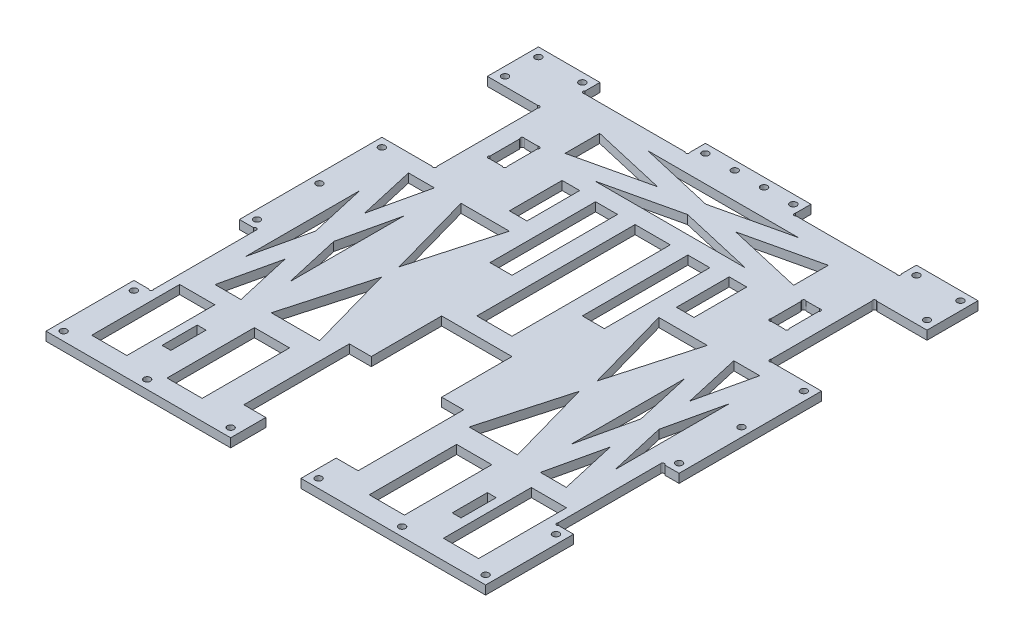
SolidWorks part; units mm, degrees
material "7050-T73510"
ref_plane "Front Plane" through (0, 0, 0) normal (0, 0, 1) x (1, 0, 0)
ref_plane "Top Plane" through (0, 0, 0) normal (0, 1, 0) x (1, 0, 0)
ref_plane "Right Plane" through (0, 0, 0) normal (1, 0, 0) x (0, 0, -1)
sketch "Sketch1" plane through (0, 0, 0) normal (0, 1, 0) x (1, 0, 0)
  line L1 (-158.75, -177.8) -> (158.75, -177.8)
  line L2 (-158.75, -177.8) -> (-158.75, 177.8)
  line L3 (-158.75, 177.8) -> (158.75, 177.8)
  line L4 (158.75, -177.8) -> (158.75, 177.8)
  line L5 (-158.75, -177.8) -> (158.75, 177.8) construction
  line L6 (-158.75, 177.8) -> (158.75, -177.8) construction
  point P0 (0, 0)
  dimension "D1" = 355.6
  dimension "D2" = 317.5
extrude "Boss-Extrude1" add sketch "Sketch1" along normal blind 6.35
sketch "Sketch2" plane through (0, 6.35, 0) normal (0, 1, 0) x (1, 0, 0)
  line L0 (-158.75, -177.8) -> (158.75, -177.8) construction
  line L1 (-25.4, -25.4) -> (25.4, -25.4)
  line L2 (-25.4, -25.4) -> (-25.4, -177.8)
  line L3 (-25.4, -177.8) -> (25.4, -177.8)
  line L4 (25.4, -25.4) -> (25.4, -177.8)
  line L5 (-25.4, -25.4) -> (25.4, -177.8) construction
  line L6 (-25.4, -177.8) -> (25.4, -25.4) construction
  point P0 (0, -101.6)
  dimension "D1" = 152.4
  dimension "D2" = 50.8
extrude "Cut-Extrude1" cut sketch "Sketch2" against normal through all
sketch "Sketch3" plane through (0, 6.35, 0) normal (0, 1, 0) x (1, 0, 0)
  line L0 (158.75, -177.8) -> (158.75, 177.8) construction
  line L5 (146.05, 140.97) -> (120.65, 140.97)
  line L11 (146.05, 140.97) -> (146.05, 64.77)
  line L13 (146.05, 64.77) -> (120.65, 64.77)
  line L15 (120.65, 140.97) -> (120.65, 64.77)
  line L16 (158.75, 177.8) -> (-158.75, 177.8) construction
  line L17 (107.95, 90.17) -> (95.25, 90.17)
  line L18 (107.95, 90.17) -> (107.95, 115.57)
  line L19 (107.95, 115.57) -> (95.25, 115.57)
  line L20 (95.25, 90.17) -> (95.25, 115.57)
  line L21 (0, -3.4925) -> (0, 3.4925) construction
  line L22 (-95.25, 90.17) -> (-95.25, 115.57)
  line L23 (-107.95, 115.57) -> (-95.25, 115.57)
  line L24 (-107.95, 90.17) -> (-107.95, 115.57)
  line L25 (-107.95, 90.17) -> (-95.25, 90.17)
  line L26 (-120.65, 140.97) -> (-120.65, 64.77)
  line L27 (-146.05, 64.77) -> (-120.65, 64.77)
  line L28 (-146.05, 140.97) -> (-146.05, 64.77)
  line L29 (-146.05, 140.97) -> (-120.65, 140.97)
  point P14 (107.95, 102.87)
  point P15 (120.65, 102.87)
  dimension "D1" = 25.4
  dimension "D2" = 12.7
  dimension "D3" = 12.7
  dimension "D4" = 12.7
  dimension "D5" = 25.4
  dimension "D6" = 76.2
  dimension "D7" = 36.83
extrude "Cut-Extrude2" cut sketch "Sketch3" against normal through all contours L5 L15 L13 L11 | L20 L17 L18 L19 | L29 L28 L27 L26 | L24 L25 L22 L23 | L26 L27 L28 L29 region at (133.35, 6.35, -102.87) region at (101.6, 6.35, -102.87) region at (-101.6, 6.35, -102.87) region at (-133.35, 6.35, -102.87)
sketch "Sketch4" plane through (0, 6.35, 0) normal (0, 1, 0) x (1, 0, 0)
  line L0 (-158.75, 177.8) -> (-158.75, -177.8) construction
  line L1 (-158.75, 140.97) -> (-146.05, 140.97)
  line L2 (-158.75, 140.97) -> (-158.75, 64.77)
  line L3 (-158.75, 64.77) -> (-146.05, 64.77)
  line L4 (-146.05, 140.97) -> (-146.05, 64.77)
  line L5 (0, -3.4925) -> (0, 3.4925) construction
  line L6 (-158.75, -114.3) -> (-146.05, -114.3)
  line L7 (-158.75, -114.3) -> (-158.75, -38.1)
  line L8 (-158.75, -38.1) -> (-146.05, -38.1)
  line L9 (-146.05, -114.3) -> (-146.05, -38.1)
  line L10 (158.75, 64.77) -> (146.05, 64.77)
  line L11 (146.05, 140.97) -> (146.05, 64.77)
  line L12 (158.75, 140.97) -> (146.05, 140.97)
  line L13 (158.75, 140.97) -> (158.75, 64.77)
  line L14 (158.75, -38.1) -> (146.05, -38.1)
  line L15 (146.05, -114.3) -> (146.05, -38.1)
  line L16 (158.75, -114.3) -> (146.05, -114.3)
  line L17 (158.75, -114.3) -> (158.75, -38.1)
  line L18 (158.75, 177.8) -> (-158.75, 177.8) construction
  line L19 (114.3, 165.1) -> (38.1, 165.1)
  line L20 (-114.3, 177.8) -> (-38.1, 177.8)
  line L21 (-114.3, 177.8) -> (-114.3, 165.1)
  line L22 (-114.3, 165.1) -> (-38.1, 165.1)
  line L23 (-38.1, 177.8) -> (-38.1, 165.1)
  line L24 (38.1, 177.8) -> (38.1, 165.1)
  line L25 (114.3, 177.8) -> (38.1, 177.8)
  line L26 (114.3, 177.8) -> (114.3, 165.1)
  line L27 (-25.4, -25.4) -> (-25.4, -177.8) construction
  line L28 (-25.4, -152.4) -> (-41.275, -152.4)
  line L29 (-25.4, -152.4) -> (-25.4, -76.2)
  line L30 (-25.4, -76.2) -> (-41.275, -76.2)
  line L31 (-41.275, -152.4) -> (-41.275, -76.2)
  line L32 (-158.75, -177.8) -> (-25.4, -177.8) construction
  line L33 (25.4, 101.6) -> (41.275, 101.6)
  line L34 (-25.4, 25.4) -> (-41.275, 25.4)
  line L35 (-25.4, 25.4) -> (-25.4, 101.6)
  line L36 (-25.4, 101.6) -> (-41.275, 101.6)
  line L37 (-41.275, 25.4) -> (-41.275, 101.6)
  line L38 (41.275, 25.4) -> (41.275, 101.6)
  line L39 (25.4, 25.4) -> (41.275, 25.4)
  line L40 (25.4, 25.4) -> (25.4, 101.6)
  line L41 (25.4, -76.2) -> (41.275, -76.2)
  line L42 (41.275, -152.4) -> (41.275, -76.2)
  line L43 (25.4, -152.4) -> (41.275, -152.4)
  line L44 (25.4, -152.4) -> (25.4, -76.2)
  dimension "D1" = 12.7
  dimension "D2" = 12.7
  dimension "D3" = 76.2
  dimension "D4" = 76.2
  dimension "D5" = 36.83
  dimension "D6" = 215.9
  dimension "D7" = 12.7
  dimension "D8" = 76.2
  dimension "D9" = 76.2
  dimension "D10" = 15.875
  dimension "D11" = 76.2
  dimension "D12" = 25.4
  dimension "D13" = 76.2
  dimension "D14" = 15.875
  dimension "D15" = 203.2
  dimension "D16" = 50.8
extrude "Cut-Extrude3" cut sketch "Sketch4" against normal through all
sketch "Sketch5" plane through (0, 6.35, 0) normal (0, 1, 0) x (1, 0, 0)
  line L0 (-41.275, -76.2) -> (-41.275, -152.4) construction
  line L5 (-41.275, 101.6) -> (-41.275, 25.4) construction
  line L6 (-85.725, -100.33) -> (-60.325, -100.33)
  line L7 (-133.35, -87.63) -> (-101.6, -87.63)
  line L8 (-133.35, -87.63) -> (-133.35, 52.07)
  line L9 (-133.35, 52.07) -> (-101.6, 52.07)
  line L10 (-101.6, -87.63) -> (-101.6, 52.07)
  line L11 (-133.35, -87.63) -> (-101.6, 52.07) construction
  line L12 (-133.35, 52.07) -> (-101.6, -87.63) construction
  line L13 (-82.55, 114.3) -> (82.55, 114.3)
  line L14 (-82.55, 114.3) -> (-82.55, 152.4)
  line L15 (-82.55, 152.4) -> (82.55, 152.4)
  line L16 (82.55, 114.3) -> (82.55, 152.4)
  line L17 (-82.55, 114.3) -> (82.55, 152.4) construction
  line L18 (-82.55, 152.4) -> (82.55, 114.3) construction
  line L23 (0, -3.4925) -> (0, 3.4925) construction
  line L24 (-12.7, -12.7) -> (12.7, -12.7)
  line L25 (-146.05, -114.3) -> (-146.05, -38.1) construction
  line L26 (-53.975, 102.87) -> (-66.675, 102.87)
  line L27 (-53.975, 102.87) -> (-53.975, 64.77)
  line L28 (-158.75, 64.77) -> (-158.75, -38.1) construction
  line L29 (-158.75, 64.77) -> (-120.65, 64.77) construction
  line L30 (-85.725, -100.33) -> (-85.725, -163.4194)
  line L31 (-12.7, -12.7) -> (-12.7, 101.6)
  line L32 (-12.7, 101.6) -> (12.7, 101.6)
  line L33 (12.7, -12.7) -> (12.7, 101.6)
  line L34 (-53.975, 64.77) -> (-66.675, 64.77)
  line L35 (-66.675, 102.87) -> (-66.675, 64.77)
  line L36 (53.975, 64.77) -> (66.675, 64.77)
  line L37 (-25.4, 25.4) -> (-25.4, 101.6) construction
  line L38 (-25.4, 101.6) -> (-41.275, 101.6) construction
  line L39 (-95.25, 90.17) -> (-95.25, 115.57) construction
  line L40 (-114.3, 165.1) -> (-38.1, 165.1) construction
  line L41 (-85.725, -163.4194) -> (-60.325, -163.4194)
  line L42 (-60.325, -100.33) -> (-60.325, -163.4194)
  line L43 (-139.5421, 50.6627) -> (-107.7921, -89.0373)
  line L44 (-127.1579, -89.0373) -> (-95.4079, 50.6627)
  line L45 (66.675, 102.87) -> (66.675, 64.77)
  line L46 (53.975, 102.87) -> (66.675, 102.87)
  line L47 (-83.9779, 146.2126) -> (81.1221, 108.1126)
  line L48 (-81.1221, 108.1126) -> (83.9779, 146.2126)
  line L49 (53.975, 102.87) -> (53.975, 64.77)
  line L50 (-88.9, -16.4414) -> (-53.975, -16.4414) construction
  line L51 (-127.1579, 53.4773) -> (-95.4079, -86.2227)
  line L52 (-139.5421, -86.2227) -> (-107.7921, 53.4773)
  line L53 (-88.9, 52.07) -> (-53.975, 52.07) construction
  line L54 (-88.9, 52.07) -> (-88.9, -84.9527) construction
  line L55 (-81.1221, 158.5874) -> (83.9779, 120.4874)
  line L56 (-83.9779, 120.4874) -> (81.1221, 158.5874)
  line L57 (-139.7, -100.33) -> (-114.3, -100.33)
  line L58 (-139.7, -100.33) -> (-139.7, -163.83)
  line L59 (-139.7, -163.83) -> (-114.3, -163.83)
  line L60 (-114.3, -100.33) -> (-114.3, -163.83)
  line L61 (-88.9, -84.9527) -> (-53.975, -84.9527)
  line L62 (-53.975, 52.07) -> (-53.975, -84.9527) construction
  line L63 (-107.95, -144.78) -> (-101.6, -144.78)
  line L64 (-107.95, -144.78) -> (-107.95, -119.38)
  line L65 (-107.95, -119.38) -> (-101.6, -119.38)
  line L66 (-101.6, -144.78) -> (-101.6, -119.38)
  line L67 (-107.95, -144.78) -> (-101.6, -119.38) construction
  line L68 (-107.95, -119.38) -> (-101.6, -144.78) construction
  line L69 (-88.9, -84.9527) -> (-71.4375, -22.7914)
  line L70 (-71.4375, -22.7914) -> (-53.975, -84.9527)
  line L71 (-88.9, 52.07) -> (-53.975, 52.07)
  line L72 (-88.9, 52.07) -> (-71.4375, -10.0914)
  line L73 (-71.4375, -10.0914) -> (-53.975, 52.07)
  point P5 (-117.475, -17.78)
  point P10 (0, 133.35)
  point P15 (0, 44.45)
  point P34 (-104.775, -132.08)
  point P45 (-33.3375, 101.6)
  point P87 (-114.3, -132.08)
  dimension "D3" = 12.7
  dimension "D4" = 19.05
  dimension "D5" = 139.7
  dimension "D6" = 25.4
  dimension "D7" = 12.7
  dimension "D8" = 31.75
  dimension "D9" = 25.4
  dimension "D10" = 12.7
  dimension "D11" = 165.1
  dimension "D12" = 12.7
  dimension "D13" = 12.7
  dimension "D14" = 12.7
  dimension "D17" = 25.4
  dimension "D18" = 63.5
  dimension "D19" = 12.7
  dimension "D20" = 6.35
  dimension "D21" = 38.1
  dimension "D22" = 38.1
  dimension "D23" = 25.4
  dimension "D15" = 114.3
  dimension "D16" = 12.7
  dimension "D24" = 12.7
  dimension "D25" = 12.7
  dimension "D26" = 12.7
  dimension "D27" = 15.3773
  dimension "D28" = 12.7
  dimension "D29" = 6.35
  dimension "D30" = 12.7
extrude "Cut-Extrude4" cut sketch "Sketch5" against normal through all contours L44 L7 L43 | L8 L52 L43 | L51 L52 L9 | L44 L51 L10 | L33 | L32 | L31 | L24 | L48 L13 L47 | L48 L55 L16 | L55 L56 L15 | L14 L56 L47 | L60 L57 L58 L59 | L63 L66 L65 L64 | L42 L6 L30 L41 | L26 L35 L34 L27 | L46 L49 L36 L45 | L61 L70 L69 | L71 L73 L72 region at (-73.025, 6.35, 131.8747) region at (-117.475, 6.35, 73.8975) region at (-130.229, 6.35, 17.78) region at (-104.721, 6.35, 17.78) region at (-117.475, 6.35, -38.3375) region at (0, 6.35, -118.4777) region at (-64.4466, 6.35, -133.35) region at (64.4466, 6.35, -133.35) region at (0, 6.35, -148.2223) region at (0, 6.35, -44.45) region at (-60.325, 6.35, -83.82) region at (60.325, 6.35, -83.82) region at (-127, 6.35, 132.08) region at (-104.775, 6.35, 132.08)
mirror "Mirror1" about plane through (0, 0, 0) normal (1, 0, 0) of "Cut-Extrude4"
sketch "Sketch7" plane through (0, 6.35, 0) normal (0, 1, 0) x (1, 0, 0)
  line L0 (-158.75, -177.8) -> (-25.4, -177.8) construction
  line L1 (-158.75, -114.3) -> (-158.75, -177.8) construction
  line L2 (0, -3.4925) -> (0, 3.4925) construction
  line L3 (-158.75, 177.8) -> (-158.75, 140.97) construction
  line L4 (-114.3, 177.8) -> (-158.75, 177.8) construction
  line L6 (38.1, 177.8) -> (-38.1, 177.8) construction
  line L7 (-38.1, 165.1) -> (-38.1, 177.8) construction
  line L8 (-25.4, -152.4) -> (-25.4, -177.8) construction
  line L9 (-158.75, -114.3) -> (-146.05, -114.3) construction
  line L10 (-158.75, 64.77) -> (-158.75, -38.1) construction
  line L11 (-146.05, -38.1) -> (-158.75, -38.1) construction
  line L12 (-158.75, 64.77) -> (-120.65, 64.77) construction
  circle A0 centre (-152.4, -171.45) radius 2.413
  circle A14 centre (-152.4, 171.45) radius 2.413
  circle A15 centre (-120.65, 171.45) radius 2.413
  circle A16 centre (-152.4, 147.32) radius 2.413
  circle A34 centre (-31.75, 171.45) radius 2.413
  circle A35 centre (-10.5833, 171.45) radius 2.413
  circle A36 centre (10.5833, 171.45) radius 2.413
  circle A37 centre (31.75, 171.45) radius 2.413
  circle A38 centre (-31.75, -171.45) radius 2.413
  circle A39 centre (-92.075, -171.45) radius 2.413
  circle A40 centre (-152.4, -120.65) radius 2.413
  circle A41 centre (-152.4, -31.75) radius 2.413
  circle A42 centre (-152.4, 58.42) radius 2.413
  circle A43 centre (-152.4, 13.335) radius 2.413
  circle A44 centre (31.75, -171.45) radius 2.413
  circle A45 centre (152.4, 13.335) radius 2.413
  circle A46 centre (152.4, 58.42) radius 2.413
  circle A47 centre (152.4, -31.75) radius 2.413
  circle A48 centre (152.4, -120.65) radius 2.413
  circle A49 centre (92.075, -171.45) radius 2.413
  circle A50 centre (152.4, 147.32) radius 2.413
  circle A51 centre (120.65, 171.45) radius 2.413
  circle A52 centre (152.4, 171.45) radius 2.413
  circle A53 centre (152.4, -171.45) radius 2.413
  dimension "D1" = 4.826
  dimension "D6" = 6.35
  dimension "D9" = 4.826
  dimension "D14" = 4.826
  dimension "D4" = 4.826
  dimension "D5" = 4.826
  dimension "D8" = 4.826
  dimension "D20" = 4.826
  dimension "D24" = 4.826
  dimension "D25" = 4.826
  dimension "D2" = 6.35
  dimension "D3" = 6.35
  dimension "D7" = 60.325
  dimension "D10" = 6.35
  dimension "D11" = 6.35
  dimension "D15" = 6.35
  dimension "D16" = 6.35
  dimension "D18" = 6.35
  dimension "D19" = 6.35
  dimension "D21" = 6.35
  dimension "D22" = 6.35
  dimension "D23" = 6.35
  dimension "D26" = 45.085
  dimension "D12" = 2
  dimension "D13" = 2
  dimension "D17" = 4
extrude "Cut-Extrude6" cut sketch "Sketch7" against normal through all
sketch "Sketch8" plane through (0, 6.35, 0) normal (0, 1, 0) x (1, 0, 0)
  circle A0 centre (-39.0994, 165.8837) radius 1.27
  circle A1 centre (-113.5398, 166.1174) radius 1.27
  circle A2 centre (-121.56, 140.0841) radius 1.27
  circle A3 centre (-121.5656, 65.6501) radius 1.27
  circle A4 centre (-147.253, -38.507) radius 1.27
  circle A5 centre (-147.0444, -113.51) radius 1.27
  circle A6 centre (-107.1943, 114.5493) radius 1.27
  circle A7 centre (-96.0341, 114.5709) radius 1.27
  circle A8 centre (-107.1845, 91.1833) radius 1.27
  circle A10 centre (-96.2084, 91.0033) radius 1.27
extrude "Cut-Extrude7" cut sketch "Sketch8" against normal through all
mirror "Mirror2" about plane through (0, 0, 0) normal (1, 0, 0) of "Cut-Extrude7"
